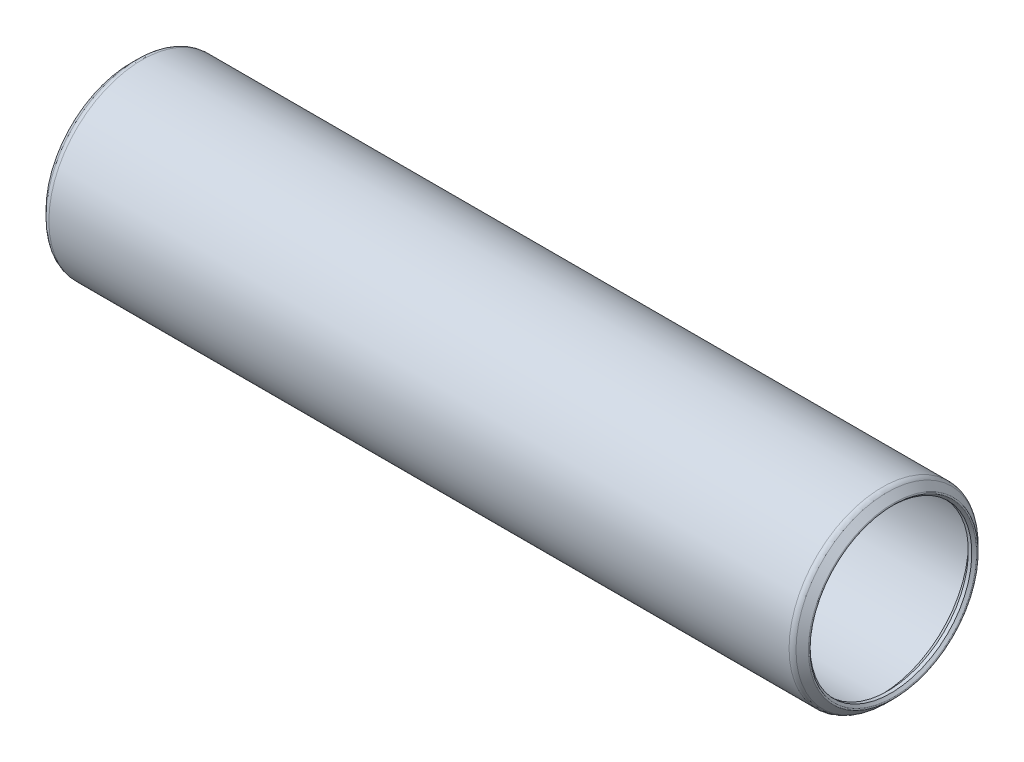
SolidWorks part; units mm, degrees
material "AISI 304"
ref_plane "Front Plane" through (0, 0, 0) normal (0, 0, 1) x (1, 0, 0)
ref_plane "Top Plane" through (0, 0, 0) normal (0, 1, 0) x (1, 0, 0)
ref_plane "Right Plane" through (0, 0, 0) normal (1, 0, 0) x (0, 0, -1)
ref_plane "Plane1" through (82.6897, 0, 0) normal (1, 0, 0) x (0, 0, -1)
sketch "Sketch1" plane through (0, 0, 0) normal (0, 0, 1) x (1, 0, 0)
  line L0 (-0.6395, 9.1676) -> (-0.381, 8.9091)
  line L1 (-0.381, 8.9091) -> (0, 8.9091)
  line L2 (0, 8.9091) -> (0.762, 9.671)
  line L3 (0.762, 9.671) -> (81.9277, 9.671)
  line L4 (81.9277, 9.671) -> (82.6897, 8.9091)
  line L5 (82.6897, 8.9091) -> (83.0707, 8.9091)
  line L6 (83.0707, 8.9091) -> (83.3292, 9.1676)
  line L7 (83.3292, 9.3472) -> (82.6443, 10.0321)
  line L8 (82.1055, 10.2553) -> (0.5842, 10.2553)
  line L9 (0.0454, 10.0321) -> (-0.6395, 9.3472)
  line L10 (82.6897, 0) -> (0, 0) construction
  arc A0 (-0.6395, 9.3472) -> (-0.6395, 9.1676) centre (-0.5497, 9.2574) ccw
  arc A1 (83.3292, 9.1676) -> (83.3292, 9.3472) centre (83.2394, 9.2574) ccw
  arc A2 (82.6443, 10.0321) -> (82.1055, 10.2553) centre (82.1055, 9.4933) ccw
  arc A3 (0.5842, 10.2553) -> (0.0454, 10.0321) centre (0.5842, 9.4933) ccw
revolve "Revolve1" add sketch "Sketch1" angle 360 about L10 reverse direction yes
ref_plane "Plane2" through (41.3449, 0, 0) normal (1, 0, 0) x (0, 0, -1)
ref_plane "cp1 XY" through (41.3449, 0, 0) normal (1, 0, 0) x (0, 0, -1)
ref_plane "cp1 XZ" through (0, 10.2553, 0) normal (0, -1, 0) x (-1, 0, 0)
ref_plane "cp1 YZ" through (0, 0, 0) normal (0, 0, -1) x (-1, 0, 0)
ref_axis "cp1 X" through (41.3449, 10.2553, 80.9) along (0, 0, -1)
ref_axis "cp1 Y" through (41.3449, -50, 0) along (0, 1, 0)
ref_axis "cp1 Z" through (80.9, 10.2553, 0) along (-1, 0, 0)
sketch3d "cp1"
  point P0 (41.3449, 10.2553, 0)
ref_plane "cp2 XY" through (41.3449, 0, 0) normal (1, 0, 0) x (0, 0, -1)
ref_plane "cp2 XZ" through (0, 0, 0) normal (0, -1, 0) x (-1, 0, 0)
ref_plane "cp2 YZ" through (0, 0, -10.2553) normal (0, 0, -1) x (-1, 0, 0)
ref_axis "cp2 X" through (41.3449, 0, 80.9) along (0, 0, -1)
ref_axis "cp2 Y" through (41.3449, -50, -10.2553) along (0, 1, 0)
ref_axis "cp2 Z" through (80.9, 0, -10.2553) along (-1, 0, 0)
sketch3d "cp2"
  point P0 (41.3449, 0, -10.2553)
ref_plane "cp3 XY" through (41.3449, 0, 0) normal (1, 0, 0) x (0, 0, -1)
ref_plane "cp3 XZ" through (0, -10.2553, 0) normal (0, -1, 0) x (-1, 0, 0)
ref_plane "cp3 YZ" through (0, 0, 0) normal (0, 0, -1) x (-1, 0, 0)
ref_axis "cp3 X" through (41.3449, -10.2553, 80.9) along (0, 0, -1)
ref_axis "cp3 Y" through (41.3449, -50, 0) along (0, 1, 0)
ref_axis "cp3 Z" through (80.9, -10.2553, 0) along (-1, 0, 0)
sketch3d "cp3"
  point P0 (41.3449, -10.2553, 0)
ref_plane "cp4 XY" through (41.3449, 0, 0) normal (1, 0, 0) x (0, 0, -1)
ref_plane "cp4 XZ" through (0, 0, 0) normal (0, -1, 0) x (-1, 0, 0)
ref_plane "cp4 YZ" through (0, 0, 10.2553) normal (0, 0, -1) x (-1, 0, 0)
ref_axis "cp4 X" through (41.3449, 0, 80.9) along (0, 0, -1)
ref_axis "cp4 Y" through (41.3449, -50, 10.2553) along (0, 1, 0)
ref_axis "cp4 Z" through (80.9, 0, 10.2553) along (-1, 0, 0)
sketch3d "cp4"
  point P0 (41.3449, 0, 10.2553)
ref_plane "tube_front XY" through (0, 0, 0) normal (1, 0, 0) x (0, 0, -1)
ref_plane "tube_front XZ" through (0, 0, 0) normal (0, -1, 0) x (-1, 0, 0)
ref_plane "tube_front YZ" through (0, 0, 0) normal (0, 0, -1) x (-1, 0, 0)
ref_axis "tube_front X" through (0, 0, 80.9) along (0, 0, -1)
ref_axis "tube_front Y" through (0, -50, 0) along (0, 1, 0)
ref_axis "tube_front Z" through (80.9, 0, 0) along (-1, 0, 0)
sketch3d "tube_front"
  point P0 (0, 0, 0)
ref_plane "tube_rear XY" through (82.6897, 0, 0) normal (1, 0, 0) x (0, 0, -1)
ref_plane "tube_rear XZ" through (0, 0, 0) normal (0, -1, 0) x (-1, 0, 0)
ref_plane "tube_rear YZ" through (0, 0, 0) normal (0, 0, -1) x (-1, 0, 0)
ref_axis "tube_rear X" through (82.6897, 0, 80.9) along (0, 0, -1)
ref_axis "tube_rear Y" through (82.6897, -50, 0) along (0, 1, 0)
ref_axis "tube_rear Z" through (80.9, 0, 0) along (-1, 0, 0)
sketch3d "tube_rear"
  point P0 (82.6897, 0, 0)
